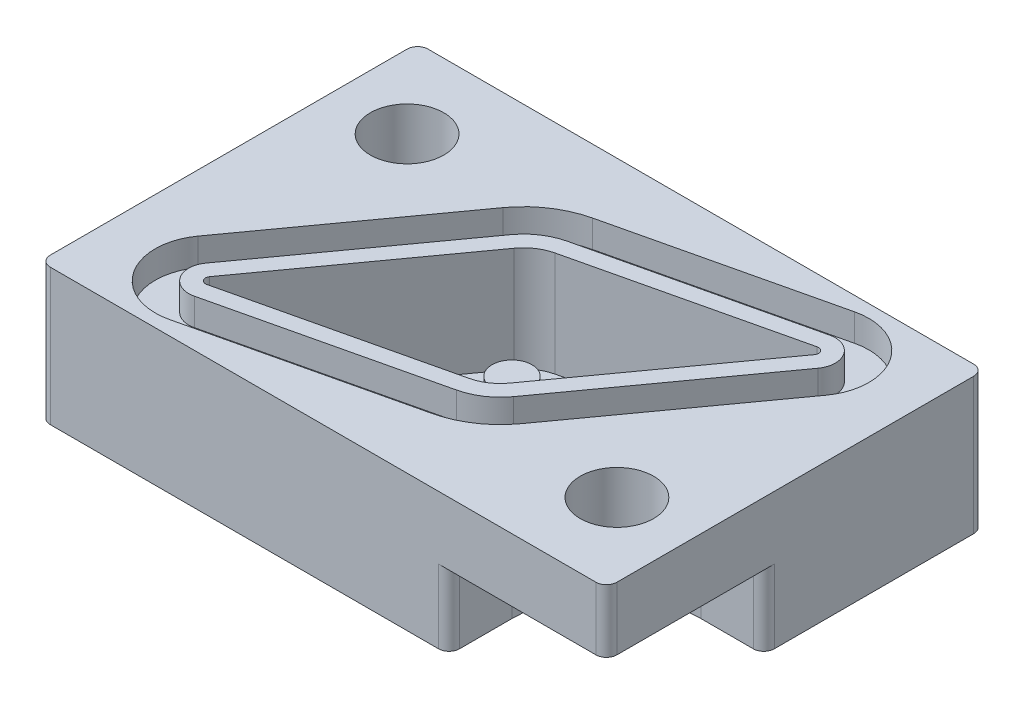
SolidWorks part; units mm, degrees
material "6061-T6 (SS)"
ref_plane "Front Plane" through (0, 0, 0) normal (0, 0, 1) x (1, 0, 0)
ref_plane "Top Plane" through (0, 0, 0) normal (0, 1, 0) x (1, 0, 0)
ref_plane "Right Plane" through (0, 0, 0) normal (1, 0, 0) x (0, 0, -1)
sketch "BaseS" plane through (0, 0, 0) normal (0, 1, 0) x (1, 0, 0)
  line L1 (-13.5, 9) -> (13.5, 9)
  line L2 (-13.5, 9) -> (-13.5, -9)
  line L3 (-13.5, -9) -> (13.5, -9)
  line L4 (13.5, 9) -> (13.5, -9)
  line L5 (-13.5, 9) -> (13.5, -9) construction
  line L6 (-13.5, -9) -> (13.5, 9) construction
  point P0 (0, 0)
  dimension "YDim" = 18
  dimension "XDim" = 27
extrude "Base" add sketch "BaseS" along normal blind 6.5
sketch "DiamondCutS" plane through (0, 6.5, 0) normal (0, 1, 0) x (1, 0, 0)
  line L4 (-13.5, -9) -> (13.5, 9) construction
  line L5 (-1.566, 3.6113) -> (8.5546, 5.9845)
  line L6 (8.8144, 5.5948) -> (2.7312, -2.8345)
  line L7 (1.566, -3.6113) -> (-8.5546, -5.9845)
  line L8 (-8.8144, -5.5948) -> (-2.7312, 2.8345)
  line L9 (2.2938, -3.4406) -> (-2.2938, 3.4406) construction
  arc A4 (8.5546, 5.9845) -> (8.8144, 5.5948) centre (8.6117, 5.7411) cw
  arc A5 (-8.8144, -5.5948) -> (-8.5546, -5.9845) centre (-8.6117, -5.7411) ccw
  arc A6 (1.566, -3.6113) -> (2.7312, -2.8345) centre (1.1094, -1.6641) ccw
  arc A7 (-1.566, 3.6113) -> (-2.7312, 2.8345) centre (-1.1094, 1.6641) ccw
  point P2 (-8.8197, -5.8798)
  point P10 (9.2059, 6.1373)
  point P13 (-9.2059, -6.1373)
  point P14 (8.8197, 5.8798)
  point P15 (2.2188, -3.3282)
  point P24 (-2.2188, 3.3282)
  dimension "D1" = 0.25
  dimension "D2" = 2
  dimension "Width" = 8
  dimension "Length" = 21.2
extrude "DiamondCut" cut sketch "DiamondCutS" against normal offset from surface (5 mm away) 1.5 up to face at (0, 0, 0)
sketch "O-RingProfileS" plane through (0, 6.5, 0) normal (0, 1, 0) x (1, 0, 0)
  line L0 (4.6773, -4.239) -> (10.7606, 4.1904)
  line L1 (8.0067, 8.3212) -> (-2.1139, 5.9479)
  line L2 (-4.6773, 4.239) -> (-10.7606, -4.1904)
  line L3 (-8.0067, -8.3212) -> (2.1139, -5.9479)
  line L16 (3.3799, -3.3027) -> (9.4632, 5.1267)
  line L17 (8.372, 6.7634) -> (-1.7487, 4.3902)
  line L18 (-3.3799, 3.3027) -> (-9.4632, -5.1267)
  line L19 (-8.372, -6.7634) -> (1.7487, -4.3902)
  line L20 (2.7312, -2.8345) -> (8.8144, 5.5948)
  line L21 (-8.5546, -5.9845) -> (1.566, -3.6113)
  line L22 (-2.7312, 2.8345) -> (-8.8144, -5.5948)
  line L23 (8.5546, 5.9845) -> (-1.566, 3.6113)
  line L24 (2.7312, -2.8345) -> (8.8144, 5.5948) construction
  line L25 (-8.5546, -5.9845) -> (1.566, -3.6113) construction
  line L26 (-2.7312, 2.8345) -> (-8.8144, -5.5948) construction
  line L27 (8.5546, 5.9845) -> (-1.566, 3.6113) construction
  arc A0 (10.7606, 4.1904) -> (8.0067, 8.3212) centre (8.6117, 5.7411) ccw
  arc A1 (-2.1139, 5.9479) -> (-4.6773, 4.239) centre (-1.1094, 1.6641) ccw
  arc A2 (-10.7606, -4.1904) -> (-8.0067, -8.3212) centre (-8.6117, -5.7411) ccw
  arc A3 (2.1139, -5.9479) -> (4.6773, -4.239) centre (1.1094, -1.6641) ccw
  arc A16 (9.4632, 5.1267) -> (8.372, 6.7634) centre (8.6117, 5.7411) ccw
  arc A17 (-1.7487, 4.3902) -> (-3.3799, 3.3027) centre (-1.1094, 1.6641) ccw
  arc A18 (-9.4632, -5.1267) -> (-8.372, -6.7634) centre (-8.6117, -5.7411) ccw
  arc A19 (1.7487, -4.3902) -> (3.3799, -3.3027) centre (1.1094, -1.6641) ccw
  arc A20 (8.8144, 5.5948) -> (8.5546, 5.9845) centre (8.6117, 5.7411) ccw
  arc A21 (1.566, -3.6113) -> (2.7312, -2.8345) centre (1.1094, -1.6641) ccw
  arc A22 (-8.8144, -5.5948) -> (-8.5546, -5.9845) centre (-8.6117, -5.7411) ccw
  arc A23 (-1.566, 3.6113) -> (-2.7312, 2.8345) centre (-1.1094, 1.6641) ccw
  arc A24 (8.8144, 5.5948) -> (8.5546, 5.9845) centre (8.6117, 5.7411) ccw construction
  arc A25 (1.566, -3.6113) -> (2.7312, -2.8345) centre (1.1094, -1.6641) ccw construction
  arc A26 (-8.8144, -5.5948) -> (-8.5546, -5.9845) centre (-8.6117, -5.7411) ccw construction
  arc A27 (-1.566, 3.6113) -> (-2.7312, 2.8345) centre (-1.1094, 1.6641) ccw construction
  dimension "D1" = 0
  dimension "BorderThickness" = 0.8
  dimension "Width" = 1.6
extrude "O-RingProfile" cut sketch "O-RingProfileS" against normal blind 1.3
sketch "SpringRetentionS" plane through (0, 0, 0) normal (1, 0, 0) x (0, 0, -1)
  line L1 (0, 1.5) -> (0.95, 1.5)
  line L2 (0, 1.5) -> (0, 4) construction
  line L3 (0.95, 1.5) -> (0.95, 4)
  line L4 (0.95, 4) -> (0, 4)
  line L5 (5.9911, 1.5) -> (5.5948, 1.5) construction
  line L6 (0, 4) -> (0, 1.5)
  dimension "D1" = 1.9
  dimension "Height" = 2.5
revolve "SpringRetention" add sketch "SpringRetentionS" angle 360 about L2
hole_wizard "M3 Clearance Hole1" positions "Sketch3" profile "Sketch4" hole size "M3" standard "ANSI Metric" end condition through all
sketch "Sketch3" plane through (0, 6.5, 0) normal (0, -1, 0) x (-1, 0, 0)
  line L2 (13.5, -9) -> (-13.5, -9) construction
  line L3 (-13.5, -9) -> (-13.5, 9) construction
  line L4 (10, 5) -> (-10, -5) construction
  point P0 (10, 5)
  point P13 (-10, -5)
  dimension "D3" = 10
  dimension "D4" = 20
  dimension "YDim" = 4
  dimension "XDim" = 3.5
sketch "Sketch4" plane through (-10, 6.5, -5) normal (1, 0, 0) x (0, 0, 1)
  line L0 (0, 0) -> (0, 6.5)
  line L1 (0, 6.5) -> (1.75, 6.5)
  line L2 (1.75, 6.5) -> (1.75, 0)
  line L5 (1.75, 0) -> (0, 0)
  line L11 (0, -6.35) -> (0, 107.95) construction
  dimension "Thru Hole Dia." = 3.5
  dimension "Thru Hole Depth" = 6.5
ref_axis "PocketCirclePattern" through (0, 6.825, 0) along (0, -1, 0)
sketch "MountingHoleCutsS" plane through (0, 0, 0) normal (0, -1, 0) x (1, 0, 0)
  line L0 (13.5, 1.5) -> (13.5, 9)
  line L1 (-13.5, -9) -> (-6, -9)
  line L2 (-13.5, -9) -> (-13.5, -1.5)
  line L3 (-13.5, -1.5) -> (-10.5, -1.5)
  line L4 (-6, -9) -> (-6, -6)
  line L5 (13.5, 9) -> (13.5, -9) construction
  line L6 (13.5, 9) -> (6, 9)
  line L7 (-13.5, 9) -> (13.5, 9) construction
  line L8 (6, 9) -> (6, 6)
  line L9 (10.5, 1.5) -> (13.5, 1.5)
  arc A0 (-6, -6) -> (-10.5, -1.5) centre (-10.5, -6) ccw
  arc A1 (6, 6) -> (10.5, 1.5) centre (10.5, 6) ccw
  dimension "D3" = 4.5
  dimension "D4" = 4.5
  dimension "D1" = 7.5
  dimension "D2" = 7.5
extrude "MountingHoleCuts" cut sketch "MountingHoleCutsS" against normal offset from surface (3.5 mm away) 3 up to face at (-10, 6.5, -3.25)
fillet "BaseF" radius 0.5 8 edges at (13.5, 3.25, -9) (13.5, 5, 9) (-13.5, 5, -9) (-13.5, 3.25, 9) (-6, 1.75, -9) (-13.5, 1.75, -1.5) (13.5, 1.75, 1.5) (6, 1.75, 9)
sketch "RefPathS" plane through (0, 5.2, 0) normal (0, 1, 0) x (1, 0, 0)
  line L0 (4.0286, -3.7708) -> (10.1119, 4.6585) construction
  line L1 (8.1894, 7.5423) -> (-1.9313, 5.169) construction
  line L2 (-4.0286, 3.7708) -> (-10.1119, -4.6585) construction
  line L3 (-8.1894, -7.5423) -> (1.9313, -5.169) construction
  line L4 (4.6773, -4.239) -> (10.7606, 4.1904)
  line L5 (8.0067, 8.3212) -> (-2.1139, 5.9479)
  line L6 (-4.6773, 4.239) -> (-10.7606, -4.1904)
  line L7 (-8.0067, -8.3212) -> (2.1139, -5.9479)
  line L8 (4.6773, -4.239) -> (10.7606, 4.1904)
  line L9 (8.0067, 8.3212) -> (-2.1139, 5.9479)
  line L10 (-4.6773, 4.239) -> (-10.7606, -4.1904)
  line L11 (-8.0067, -8.3212) -> (2.1139, -5.9479)
  line L12 (3.3117, 5.5768) -> (2.9464, 7.1345) construction
  line L13 (8.372, 6.7634) -> (-1.7487, 4.3902) construction
  arc A0 (10.1119, 4.6585) -> (8.1894, 7.5423) centre (8.6117, 5.7411) ccw construction
  arc A1 (-1.9313, 5.169) -> (-4.0286, 3.7708) centre (-1.1094, 1.6641) ccw construction
  arc A2 (-10.1119, -4.6585) -> (-8.1894, -7.5423) centre (-8.6117, -5.7411) ccw construction
  arc A3 (1.9313, -5.169) -> (4.0286, -3.7708) centre (1.1094, -1.6641) ccw construction
  arc A4 (2.1139, -5.9479) -> (4.6773, -4.239) centre (1.1094, -1.6641) ccw
  arc A5 (10.7606, 4.1904) -> (8.0067, 8.3212) centre (8.6117, 5.7411) ccw
  arc A6 (-2.1139, 5.9479) -> (-4.6773, 4.239) centre (-1.1094, 1.6641) ccw
  arc A7 (-10.7606, -4.1904) -> (-8.0067, -8.3212) centre (-8.6117, -5.7411) ccw
  arc A8 (2.1139, -5.9479) -> (4.6773, -4.239) centre (1.1094, -1.6641) ccw
  arc A9 (10.7606, 4.1904) -> (8.0067, 8.3212) centre (8.6117, 5.7411) ccw
  arc A10 (-2.1139, 5.9479) -> (-4.6773, 4.239) centre (-1.1094, 1.6641) ccw
  arc A11 (-10.7606, -4.1904) -> (-8.0067, -8.3212) centre (-8.6117, -5.7411) ccw
  point P28 (3.129, 6.3557)
  point P29 (0, 0)
  dimension "D2" = 3.6
  dimension "D3" = 1.85
  dimension "D4" = 20.7
  dimension "D1" = 0
